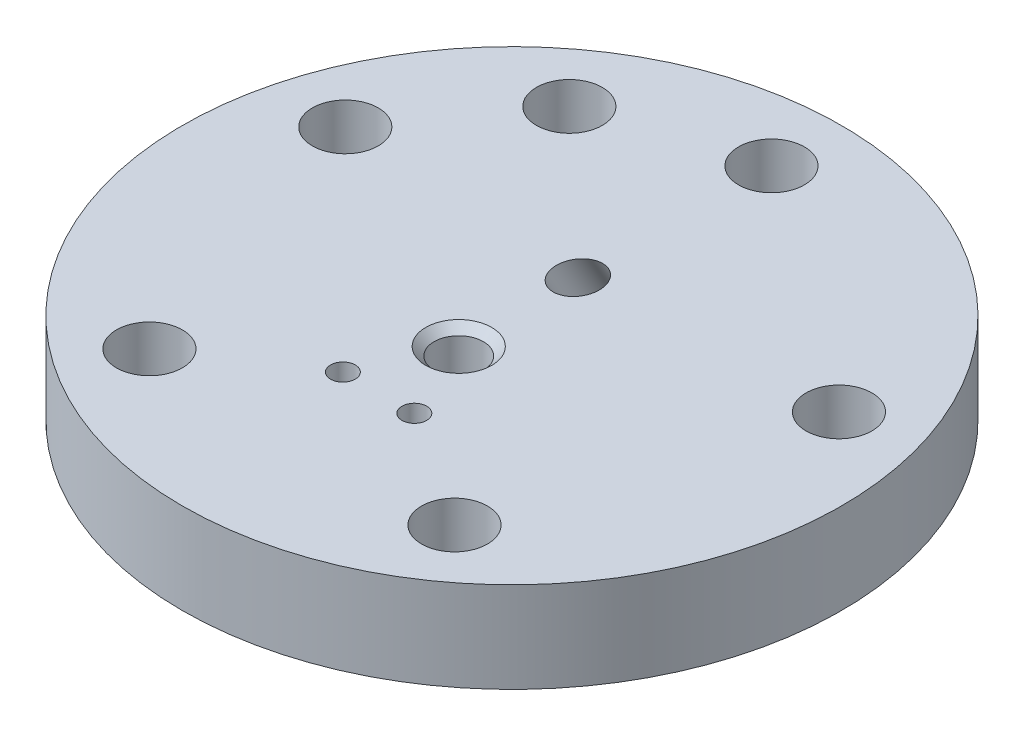
SolidWorks part; units mm, degrees
ref_plane "前视基准面" through (0, 0, 0) normal (0, 0, 1) x (1, 0, 0)
ref_plane "上视基准面" through (0, 0, 0) normal (0, 1, 0) x (1, 0, 0)
ref_plane "右视基准面" through (0, 0, 0) normal (1, 0, 0) x (0, 0, -1)
sketch "草图1" plane through (0, 0, 0) normal (0, 1, 0) x (1, 0, 0)
  line L0 (0, 0) -> (-18.5152, 25.484) construction
  line L1 (0, 0) -> (-55.6938, 0) construction
  circle A0 centre (0, 0) radius 40
  circle A1 centre (0, 0) radius 31.5 construction
  circle A2 centre (0, 31.5) radius 4
  circle A3 centre (29.9583, 9.734) radius 4
  circle A4 centre (18.5152, -25.484) radius 4
  circle A5 centre (-18.5152, -25.484) radius 4
  circle A6 centre (-29.9583, 9.734) radius 4
  circle A7 centre (-18.5152, 25.484) radius 4
  dimension "D1" = 80
  dimension "D2" = 63
  dimension "D3" = 8
  dimension "D5" = 8
  dimension "D6" = 54
  dimension "D4" = 5
extrude "凸台-拉伸1" add sketch "草图1" along normal blind 11
sketch "草图3" plane through (0, 11, 0) normal (0, 1, 0) x (1, 0, 0)
  circle A0 centre (0, -6.456) radius 3
  dimension "D1" = 6
extrude "切除-拉伸1" cut sketch "草图3" against normal through all
chamfer "倒角1" distance 1 angle 45 1 edges at (0, 11, 9.456)
ref_axis "基准轴1" through (-44, 0, 0) along (1, 0, 0)
sketch "草图5" plane through (0, 11, 0) normal (0, 1, 0) x (1, 0, 0)
  line L0 (-44, 0) -> (44, 0) construction
  point P0 (0, 8)
  dimension "D1" = 8
ref_point "点3"
ref_plane "基准面1" through (0, 0, 0) normal (0, 0.866, 0.5) x (1, 0, 0)
sketch "草图6" plane through (0, 0, 0) normal (0, 0.866, 0.5) x (1, 0, 0)
  circle A0 centre (0, 12.4282) radius 2.6
  dimension "D1" = 5.2
extrude "切除-拉伸2" cut sketch "草图6" against normal mid plane 20
sketch "草图7" plane through (0, 11, 0) normal (0, 1, 0) x (1, 0, 0)
  line L0 (0, 0) -> (-4.3352, -16.1793) construction
  line L1 (0, 0) -> (0, -23.793) construction
  circle A0 centre (0, 0) radius 16.75 construction
  circle A1 centre (-4.3352, -16.1793) radius 1.5
  circle A2 centre (4.3352, -16.1793) radius 1.5
  dimension "D1" = 33.5
  dimension "D2" = 3
  dimension "D4" = 15
extrude "切除-拉伸3" cut sketch "草图7" against normal blind 8
